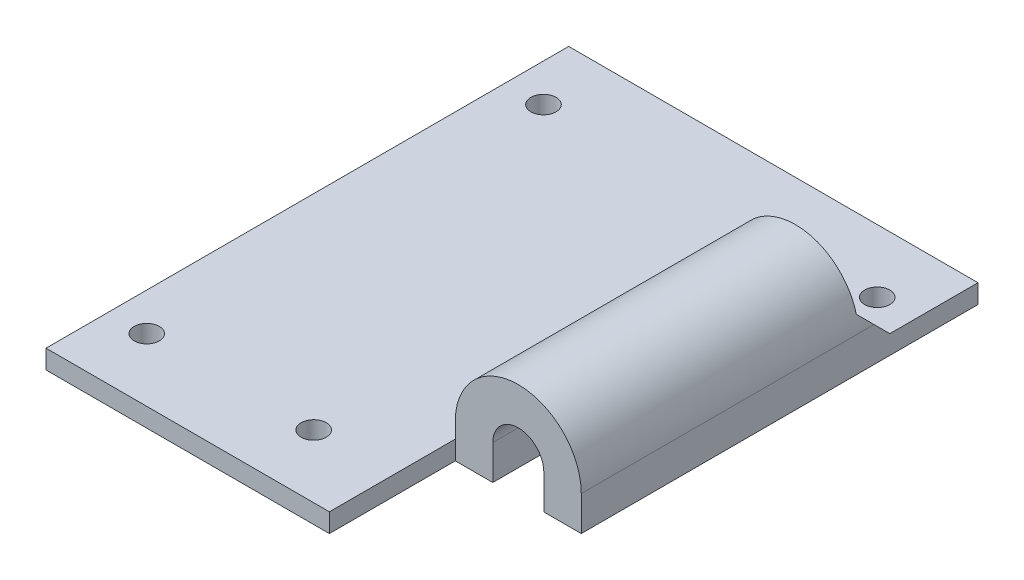
SolidWorks part; units mm, degrees
ref_plane "Front Plane" through (0, 0, 0) normal (0, 0, 1) x (1, 0, 0)
ref_plane "Top Plane" through (0, 0, 0) normal (0, 1, 0) x (1, 0, 0)
ref_plane "Right Plane" through (0, 0, 0) normal (1, 0, 0) x (0, 0, -1)
sketch "Sketch1" plane through (0, 0, 0) normal (0, 1, 0) x (1, 0, 0)
  line L0 (45, -83) -> (45, -63)
  line L1 (0, 0) -> (65, 0)
  line L2 (0, 0) -> (0, -83)
  line L3 (0, -83) -> (45, -83)
  line L4 (65, 0) -> (65, -63)
  line L5 (45, -63) -> (65, -63)
  dimension "D1" = 65
  dimension "D2" = 83
  dimension "D3" = 20
  dimension "D4" = 45
extrude "Boss-Extrude1" add sketch "Sketch1" along normal blind 3
sketch "Sketch3" plane through (0, 3, 0) normal (0, 1, 0) x (1, 0, 0)
  line L0 (0, -10) -> (65, -10) construction
  line L1 (0, 0) -> (0, -83) construction
  line L2 (65, -63) -> (65, 0) construction
  line L3 (0, -73) -> (45, -73) construction
  line L4 (0, 0) -> (0, -83) construction
  line L5 (45, -83) -> (45, -63) construction
  circle A0 centre (6, -10) radius 2
  circle A1 centre (59, -10) radius 2
  circle A2 centre (6, -73) radius 2
  circle A3 centre (32.5, -73) radius 2
  dimension "D1" = 4
  dimension "D2" = 6
  dimension "D3" = 6
  dimension "D4" = 6
  dimension "D5" = 26.5
extrude "Cut-Extrude1" cut sketch "Sketch3" against normal blind 5
sketch "Sketch4" plane through (0, 0, 63) normal (0, 0, 1) x (1, 0, 0)
  line L0 (45, 3) -> (45, 5.5)
  line L1 (65, 5.5) -> (65, 3)
  line L2 (45, 3) -> (65, 3) construction
  line L3 (45, 3) -> (65, 3)
  line L9 (45, 3) -> (45, 0)
  line L10 (45, 0) -> (65, 0)
  line L13 (65, 0) -> (65, 3)
  line L14 (65, 3) -> (45, 3)
  line L15 (45, 3) -> (45, 0)
  line L16 (45, 0) -> (65, 0)
  line L19 (65, 0) -> (65, 3)
  arc A0 (45, 5.5) -> (65, 5.5) centre (55, 5.5) cw
  line M13 (65, 3) -> (45, 3)
  dimension "D1" = 10
  dimension "D2" = 5.5
  dimension "D3" = 0
extrude "Boss-Extrude4" add sketch "Sketch4" against normal blind 44 contours A0 L0 L1 M13 region at (55, 8.4176, 63)
sketch "Sketch6" plane through (0, 0, 63) normal (0, 0, 1) x (1, 0, 0)
  circle A0 centre (55, 5.5) radius 4.05
  dimension "D1" = 8.1
extrude "Cut-Extrude3" cut sketch "Sketch6" against normal blind 40
chamfer "Chamfer2" distance 5 angle 45 1 edges at (55, 3, 19)
sketch "Sketch7" plane through (0, 0, 63) normal (0, 0, 1) x (1, 0, 0)
  line L0 (50.95, 5.5) -> (50.95, 0)
  line L1 (45, 0) -> (65, 0) construction
  line L2 (50.95, 0) -> (59.05, 0)
  line L3 (59.05, 0) -> (59.05, 5.5)
  line L4 (59.05, 5.5) -> (50.95, 5.5)
  circle A0 centre (55, 5.5) radius 4.05 construction
extrude "Cut-Extrude4" cut sketch "Sketch7" against normal up to surface (40 mm away) up to face at (59.05, 5.5, 23)
